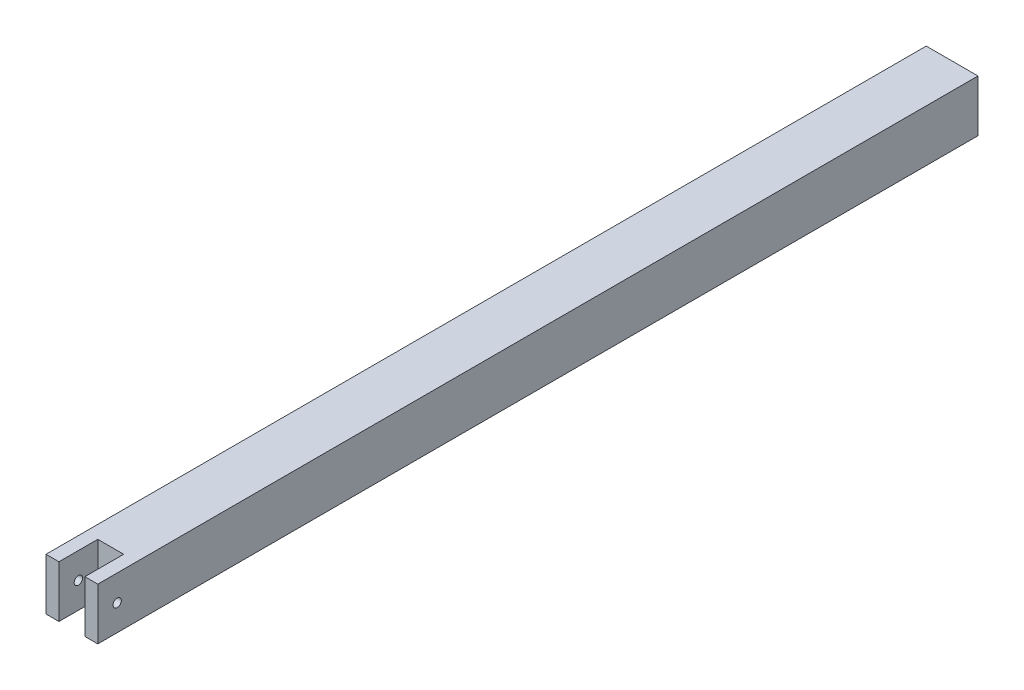
SolidWorks part; units mm, degrees
ref_plane "Front" through (0, 0, 0) normal (0, 0, 1) x (1, 0, 0)
ref_plane "Top" through (0, 0, 0) normal (0, 1, 0) x (1, 0, 0)
ref_plane "Right" through (0, 0, 0) normal (1, 0, 0) x (0, 0, -1)
sketch "Esquisse1" plane through (0, 0, 0) normal (0, 0, 1) x (1, 0, 0)
  line L1 (0, 0) -> (100, 0)
  line L2 (0, 0) -> (0, 100)
  line L3 (0, 100) -> (100, 100)
  line L4 (100, 0) -> (100, 100)
  dimension "D1" = 100
  dimension "D2" = 100
extrude "Boss.-Extru.1" add sketch "Esquisse1" along normal blind 1700
sketch "Esquisse2" plane through (0, 0, 0) normal (0, -1, 0) x (1, 0, 0)
  line L0 (0, 1700) -> (100, 1700) construction
  line L1 (25, 1700) -> (75, 1700)
  line L2 (25, 1700) -> (25, 1625)
  line L3 (25, 1625) -> (75, 1625)
  line L4 (75, 1700) -> (75, 1625)
  line L5 (50, 1625) -> (50, 1700) construction
  dimension "D1" = 50
  dimension "D2" = 75
extrude "Enlèv. mat.-Extru.1" cut sketch "Esquisse2" against normal through all
sketch "Esquisse3" plane through (100, 0, 0) normal (1, 0, 0) x (0, 0, -1)
  line L0 (-1700, 50) -> (-1662.5, 50) construction
  line L1 (-1700, 0) -> (-1700, 100) construction
  line L2 (-1662.5, 50) -> (-1625, 50) construction
  line L3 (-1625, 100) -> (-1625, 0) construction
  circle A0 centre (-1662.5, 50) radius 8
  dimension "D1" = 16
extrude "Enlèv. mat.-Extru.2" cut sketch "Esquisse3" against normal through all
